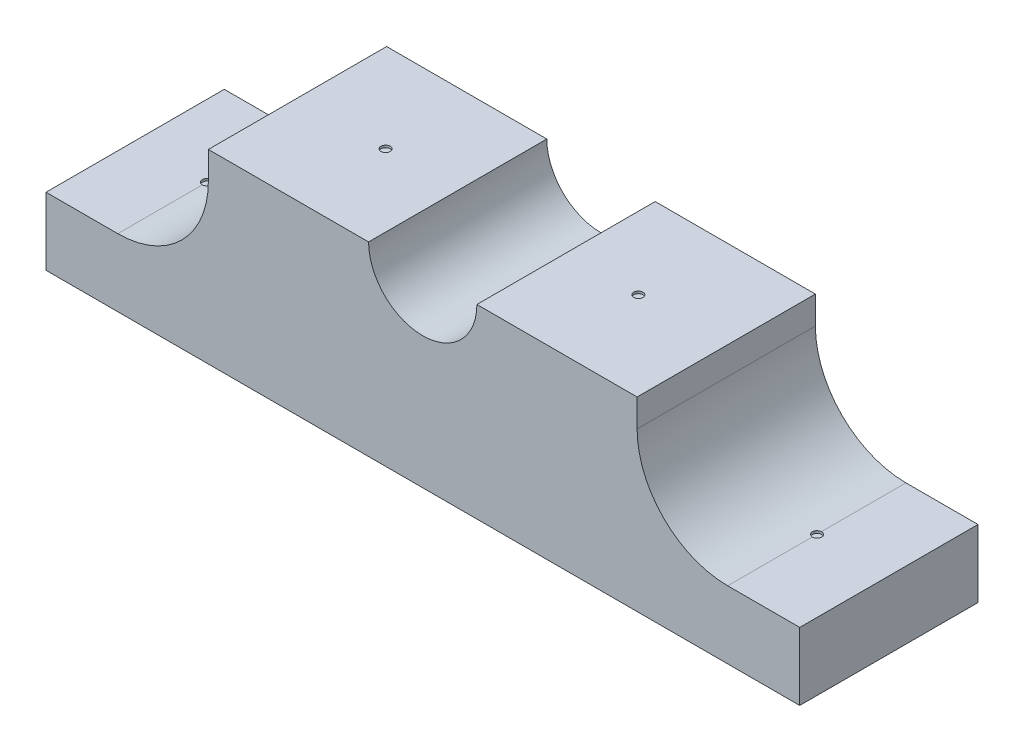
SolidWorks part; units mm, degrees
material "Custom Plastic"
ref_plane "Front Plane" through (0, 0, 0) normal (0, 0, 1) x (1, 0, 0)
ref_plane "Top Plane" through (0, 0, 0) normal (0, 1, 0) x (1, 0, 0)
ref_plane "Right Plane" through (0, 0, 0) normal (1, 0, 0) x (0, 0, -1)
sketch "Sketch2" plane through (0, 0, 0) normal (0, 1, 0) x (1, 0, 0)
  line L1 (-20.873, -4.9365) -> (20.873, -4.9365)
  line L2 (-20.873, -4.9365) -> (-20.873, 4.9365)
  line L3 (-20.873, 4.9365) -> (20.873, 4.9365)
  line L4 (20.873, -4.9365) -> (20.873, 4.9365)
  line L5 (-20.873, -4.9365) -> (20.873, 4.9365) construction
  line L6 (-20.873, 4.9365) -> (20.873, -4.9365) construction
  point P0 (0, 0)
  dimension "D1" = 41.746
  dimension "D2" = 9.873
extrude "Boss-Extrude1" add sketch "Sketch2" along normal blind 3.746 contours L1 L4 L3 L2
sketch "Sketch3" plane through (0, 3.746, 0) normal (0, 1, 0) x (1, 0, 0)
  line L0 (-11.8803, 4.9365) -> (-11.8803, -4.9365)
  line L1 (-20.873, 4.9365) -> (20.873, 4.9365) construction
  line L2 (-11.8803, 4.9365) -> (11.8657, 4.9365)
  line L3 (-20.873, -4.9365) -> (20.873, -4.9365) construction
  line L4 (-11.8803, -4.9365) -> (11.8657, -4.9365)
  line L5 (11.8657, -4.9365) -> (11.8657, 4.9365)
extrude "Boss-Extrude2" add sketch "Sketch3" along normal blind 6.5485
fillet "Fillet1" radius 5.0165 2 edges at (11.8657, 3.746, 0) (-11.8803, 3.746, 0)
sketch "Sketch4" plane through (0, 0, 4.9365) normal (0, 0, 1) x (1, 0, 0)
  line L0 (-11.8803, 10.2945) -> (11.8657, 10.2945) construction
  circle A0 centre (-0.0073, 10.2945) radius 2.9997
extrude "Cut-Extrude1" cut sketch "Sketch4" against normal through all
sketch "Sketch5" plane through (0, 10.2945, 0) normal (0, 1, 0) x (1, 0, 0)
  line L0 (-11.8803, 4.9365) -> (11.8657, 4.9365)
  line L1 (11.8657, 4.9365) -> (11.8657, -4.9365)
  line L2 (11.8657, -4.9365) -> (-11.8803, -4.9365)
  line L3 (-16.8968, -4.9365) -> (-11.8803, -4.9365) construction
  line L4 (-11.8803, -4.9365) -> (-3.0071, -4.9365) construction
  line L5 (-11.8803, -4.9365) -> (-11.8803, 4.9365)
sketch "Sketch6" plane through (0, 3.746, 0) normal (0, 1, 0) x (1, 0, 0)
  line L2 (-16.8968, -4.9365) -> (-16.8968, 4.9365) construction
  circle A0 centre (-16.8968, 0) radius 0.254
  circle A1 centre (16.8968, 0) radius 0.254
extrude "Cut-Extrude2" cut sketch "Sketch6" against normal blind 0.127 and the other way through all
sketch "Sketch7" plane through (0, 10.2945, 0) normal (0, 1, 0) x (1, 0, 0)
  circle A0 centre (-7, 0) radius 0.254
  circle A1 centre (7, 0) radius 0.254
  point P7 (0, 0)
extrude "Cut-Extrude3" cut sketch "Sketch7" against normal blind 0.127
